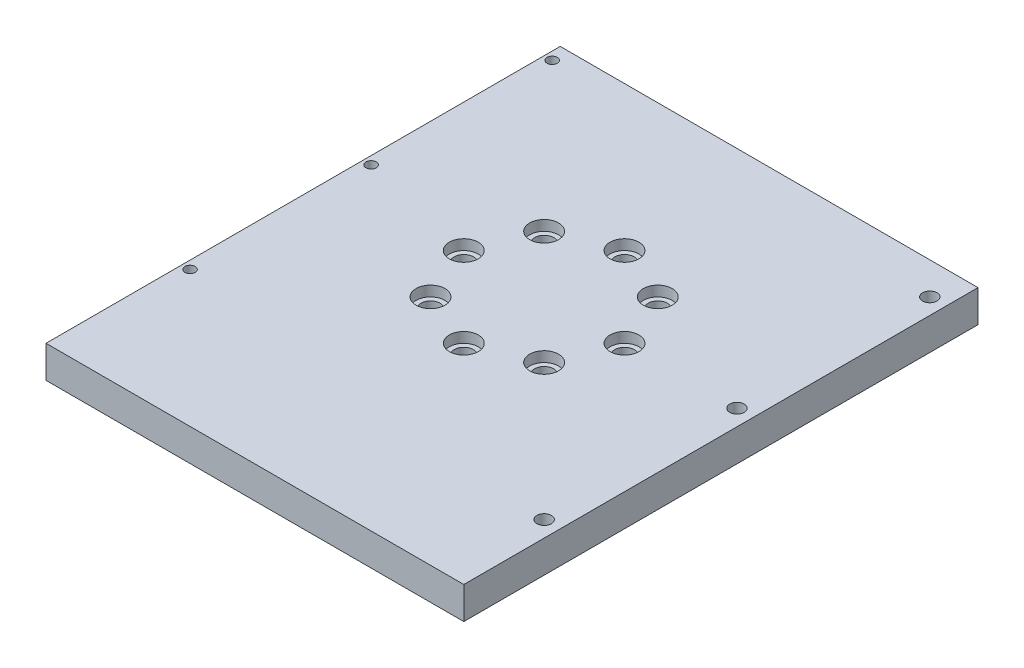
SolidWorks part; units mm, degrees
note: The reader was unsure of these and kept them because the rebuilt part matched: shared geometry of "Sketch1<8>", "Sketch1<9>".
ref_plane "Front Plane" through (0, 0, 0) normal (0, 0, 1) x (1, 0, 0)
ref_plane "Top Plane" through (0, 0, 0) normal (0, 1, 0) x (1, 0, 0)
ref_plane "Right Plane" through (0, 0, 0) normal (1, 0, 0) x (0, 0, -1)
sketch "Sketch1" plane through (0, 0, 0) normal (0, 1, 0) x (1, 0, 0)
  line L6 (-65, 70) -> (-65, -90)
  line L8 (0, 70) -> (-65, 70)
  line L10 (-65, -90) -> (0, -90)
  line L18 (0, 70) -> (65, 70)
  line L19 (0, -45) -> (0, -45.7368)
  line L20 (0, -90) -> (65, -90)
  line L21 (65, 70) -> (65, -90)
  circle A2 centre (0, 0) radius 45
  circle A3 centre (0, 0) radius 55
  circle A5 centre (0, 25) radius 3
  circle A7 centre (17.6777, 17.6777) radius 3
  circle A8 centre (25, 0) radius 3
  circle A9 centre (17.6777, -17.6777) radius 3
  circle A10 centre (0, -25) radius 3
  circle A11 centre (-17.6777, -17.6777) radius 3
  circle A12 centre (-25, 0) radius 3
  circle A13 centre (-17.6777, 17.6777) radius 3
  circle A15 centre (0, 0) radius 30 construction
  circle A17 centre (0, 25) radius 4.5
  circle A18 centre (17.6777, 17.6777) radius 4.5
  circle A19 centre (25, 0) radius 4.5
  circle A20 centre (17.6777, -17.6777) radius 4.5
  circle A21 centre (0, -25) radius 4.5
  circle A22 centre (-17.6777, -17.6777) radius 4.5
  circle A23 centre (-25, 0) radius 4.5
  circle A24 centre (-17.6777, 17.6777) radius 4.5
  circle A25 centre (0, 0) radius 70 construction
  point P10 (-65, 70)
  point P11 (0, 55)
  point P27 (0, 0)
  point P28 (0, 0)
  point P30 (0, 70)
  point P32 (0, 0)
  point P33 (0, 0)
  point P34 (0, 0)
  point P35 (0, 0)
  point P50 (0, 0)
  point P53 (0, 0)
  point P55 (0, 0)
  point P56 (0, 0)
  point P60 (0, 0)
  dimension "D1" = 110
  dimension "D2" = 90
  dimension "D4" = 25
  dimension "D6" = 1.5
  dimension "D7" = 60
  dimension "D8" = 6
  dimension "D11" = 65
  dimension "D13" = 65
  dimension "D12" = 65
  dimension "D14" = 65
  dimension "D3" = 10
  dimension "D9" = 8
  dimension "D5" = 8
extrude "Boss-Extrude1" add sketch "Sketch1" along normal blind 10
extrude "Boss-Extrude2" add sketch "Sketch1<8>" against normal blind 5 contours A3 A2
sketch "Sketch1<8>" plane through (0, 0, 0) normal (0, 1, 0) x (1, 0, 0) same geometry as "Sketch1"
fillet "Fillet1" [suppressed] radius 0.5
extrude "Boss-Extrude3" add sketch "Sketch1<9>" along normal blind 6.8 contours A20 A9 | A19 A8 | A18 A7 | A17 A5 | A24 A13 | A23 A12 | A22 A11 | A21 A10
sketch "Sketch1<9>" plane through (0, 0, 0) normal (0, 1, 0) x (1, 0, 0) same geometry as "Sketch1"
sketch "Sketch3" plane through (0, 10, 0) normal (0, 1, 0) x (1, 0, 0)
  line L0 (65, 70) -> (65, -90) construction
  point P0 (65, 0)
  dimension "D1" = 70
sketch "Sketch4" plane through (0, 10, 0) normal (0, 1, 0) x (1, 0, 0)
  line L1 (-65, 70) -> (-60, 70) construction
  line L2 (-65, 70) -> (-65, -52.69) construction
  line L3 (-65, -52.69) -> (-60, -52.69) construction
  line L4 (-60, 70) -> (-60, -52.69) construction
  line L5 (-62.5, 70) -> (-62.5, -52.69) construction
  line L6 (-65, 8.655) -> (-60, 8.655) construction
  circle A0 centre (-62.5, 65) radius 1.6
  circle A1 centre (-62.5, 8.655) radius 1.6
  circle A2 centre (-62.5, -47.69) radius 1.6
  point P13 (0, 0)
  dimension "D2" = 5
  dimension "D3" = 5
  dimension "D1" = 122.69
extrude "Cut-Extrude1" cut sketch "Sketch4" against normal blind 10
sketch "Sketch5" plane through (0, 10, 0) normal (0, 1, 0) x (1, 0, 0)
  line L0 (-65, 70) -> (65, 70) construction
  line L1 (55, 70) -> (65, 70) construction
  line L2 (55, 70) -> (55, -70) construction
  line L3 (55, -70) -> (65, -70) construction
  line L4 (65, 70) -> (65, -70) construction
  line L5 (65, 70) -> (65, -90) construction
  line L6 (60, 70) -> (60, -70) construction
  line L7 (55, 0) -> (65, 0) construction
  circle A0 centre (60, 60) radius 2.25
  circle A1 centre (60, 0) radius 2.25
  circle A2 centre (60, -60) radius 2.25
  dimension "D3" = 10
  dimension "D4" = 4.5
  dimension "D5" = 4.5
  dimension "D1" = 10
  dimension "D2" = 140
extrude "Cut-Extrude2" cut sketch "Sketch5" against normal blind 10
sketch "Sketch6" [suppressed] plane through (0, 10, 0) normal (0, 1, 0) x (1, 0, 0)
  line L0 (65, 70) -> (65, -90) construction
  line L1 (-65, -90) -> (65, -90)
  line L2 (-65, -90) -> (-65, -70)
  line L3 (-65, -70) -> (65, -70)
  line L4 (65, -90) -> (65, -70)
  dimension "D1" = 20
